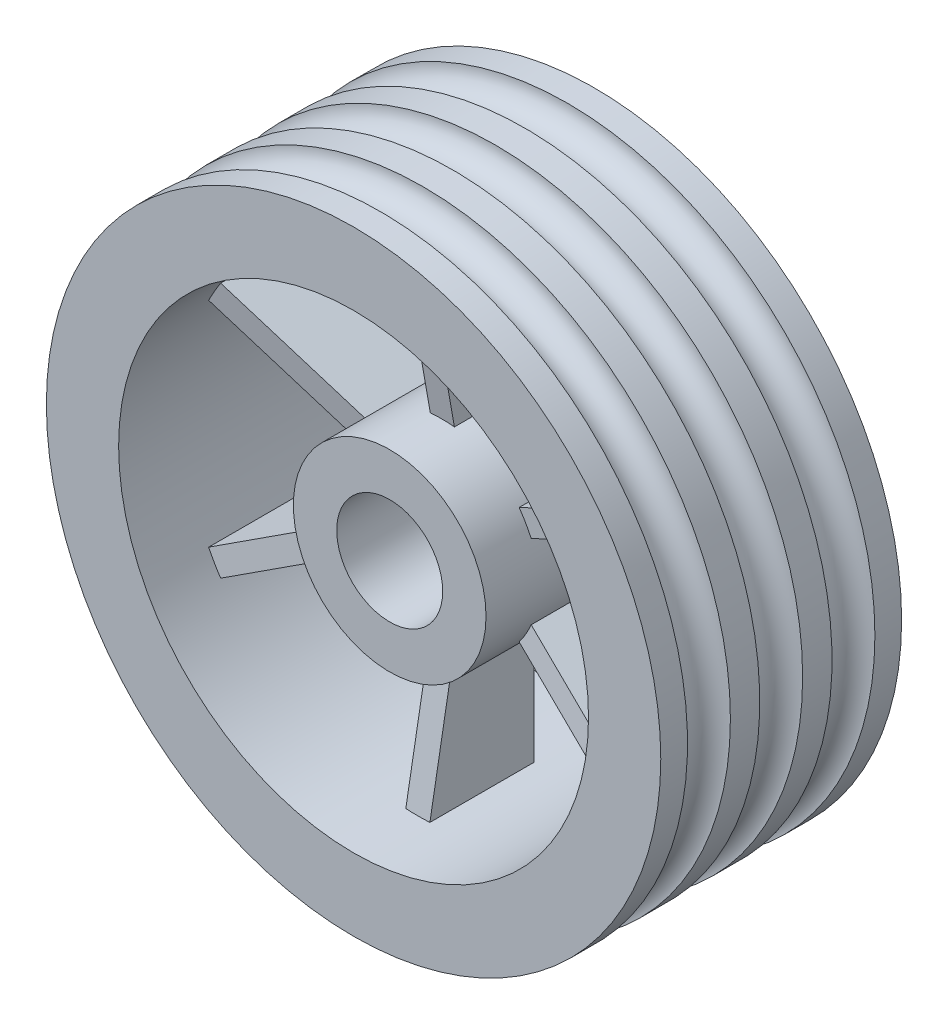
SolidWorks part; units mm, degrees
ref_plane "Front Plane" through (0, 0, 0) normal (0, 0, 1) x (1, 0, 0)
ref_plane "Top Plane" through (0, 0, 0) normal (0, 1, 0) x (1, 0, 0)
ref_plane "Right Plane" through (0, 0, 0) normal (1, 0, 0) x (0, 0, -1)
sketch "Sketch1" plane through (0, 0, 0) normal (0, 0, 1) x (1, 0, 0)
  circle A0 centre (0, 0) radius 9.755
  circle A1 centre (0, 0) radius 12.755
  dimension "D2" = 25.51
  dimension "D1" = 3
extrude "Boss-Extrude1" add sketch "Sketch1" along normal blind 10
sketch "Sketch2" plane through (0, 0, 0) normal (0, 0, 1) x (1, 0, 0)
  circle A0 centre (0, 0) radius 4
  circle A1 centre (0, 0) radius 2.2
  dimension "D1" = 8
  dimension "D2" = 4.4
extrude "Boss-Extrude2" add sketch "Sketch2" along normal blind 8.5 and the other way blind 0.5 separate body
sketch "Sketch5" plane through (0, 0, 0) normal (1, 0, 0) x (0, 0, -1)
  line L6 (-3, 2.2) -> (-3, 10.7)
  line L7 (-3, 10.7) -> (-7.5, 10.7)
  line L8 (-7.5, 10.7) -> (-6, 2.2)
  line L9 (-6, 2.2) -> (-3, 2.2)
  dimension "D1" = 2.2
  dimension "D2" = 3
  dimension "D3" = 3
  dimension "D4" = 4.5
  dimension "D5" = 8.5
extrude "Boss-Extrude3" add sketch "Sketch5" along normal blind 0.5 and the other way blind 0.5
sketch "Sketch6" plane through (0, 0, 0) normal (1, 0, 0) x (0, 0, -1)
  line L0 (0, 0) -> (-8.5, 0) construction
  line L1 (-8.5, 2.2) -> (-8.5, -2.2) construction
  line L2 (-8.5, 0) -> (-8.5, 5) construction
  line L3 (-8.5, 5) -> (-10, 9.755)
  line L4 (-10, 12.755) -> (-10, -12.755) construction
  line L5 (-10, 9.755) -> (-10, -9.755) construction
  line L7 (-7, 5) -> (-7, 9.755)
  line L8 (-7, 9.755) -> (-10, 9.755)
  line L9 (-8.5, 5) -> (-8.5, 3.4839)
  line L10 (-8.5, 3.4839) -> (-7, 3.4839)
  line L11 (-7, 3.4839) -> (-7, 5)
  dimension "D1" = 5
  dimension "D2" = 1.5
  dimension "D3" = 4.755
extrude "Boss-Extrude8" [suppressed] add sketch "Sketch6" along normal blind 0.5 and the other way blind 0.5
pattern_circular "CirPattern1" count 6 over 360 about axis through (0, 0, -0.5) along (0, 0, 1) of "Boss-Extrude3", "Boss-Extrude8" reverse direction yes
sketch "Sketch7" plane through (0, 0, 0) normal (1, 0, 0) x (0, 0, -1)
  line L0 (0, 0) -> (0, 12.755) construction
  line L2 (0, -12.755) -> (0, 12.755) construction
  line L3 (0, 12.755) -> (-10, 12.755) construction
  line L4 (-10, 12.755) -> (-10, -12.755) construction
  line L5 (0, 0) -> (-10.5402, 0) construction
  circle A0 centre (-5, 12.755) radius 0.89
  circle A1 centre (-2, 12.755) radius 0.89
  circle A2 centre (-8, 12.755) radius 0.89
  point P2 (0, 0)
  dimension "D3" = 1.78
  dimension "D1" = 12.755
  dimension "D2" = 10
  dimension "D6" = 3
  dimension "D7" = 3
  dimension "D4" = 2
  dimension "D5" = 2
revolve "Cut-Revolve1" cut sketch "Sketch7" angle 360 about L5
ref_plane "Plane1" through (0, 0, 2) normal (0, 0, -1) x (-1, 0, 0)
ref_plane "Plane2" through (0, 0, 5) normal (0, 0, -1) x (-1, 0, 0)
ref_plane "Plane3" through (0, 0, 8) normal (0, 0, -1) x (-1, 0, 0)
ref_plane "Plane4" through (0, 0, 0) normal (0, 0, -1) x (-1, 0, 0)
